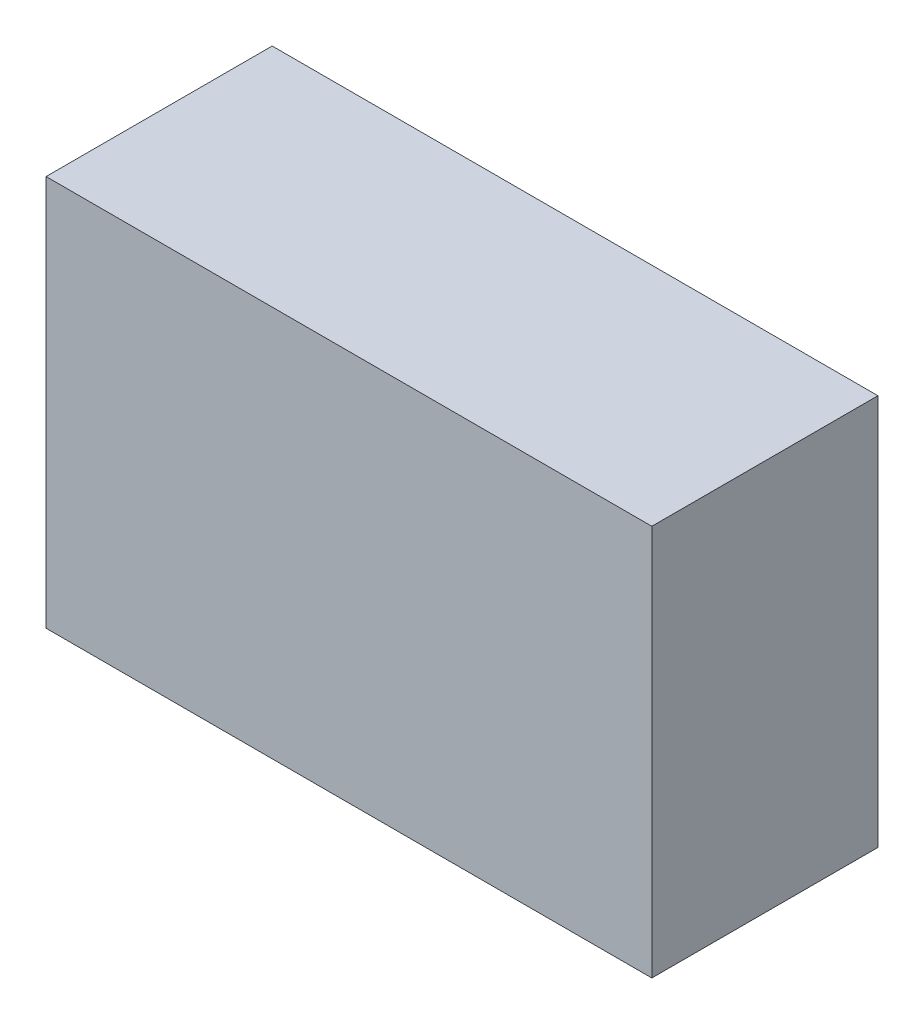
SolidWorks part; units mm, degrees
ref_plane "Front Plane" through (0, 0, 0) normal (0, 0, 1) x (1, 0, 0)
ref_plane "Top Plane" through (0, 0, 0) normal (0, 1, 0) x (1, 0, 0)
ref_plane "Right Plane" through (0, 0, 0) normal (1, 0, 0) x (0, 0, -1)
sketch "Sketch2" plane through (0, 0, 0) normal (0, 0, 1) x (1, 0, 0)
  line L1 (0, 0) -> (288, 0)
  line L2 (0, 0) -> (0, 186)
  line L3 (0, 186) -> (288, 186)
  line L4 (288, 0) -> (288, 186)
  dimension "D1" = 288
  dimension "D2" = 186
extrude "Boss-Extrude1" add sketch "Sketch2" along normal blind 107.5
